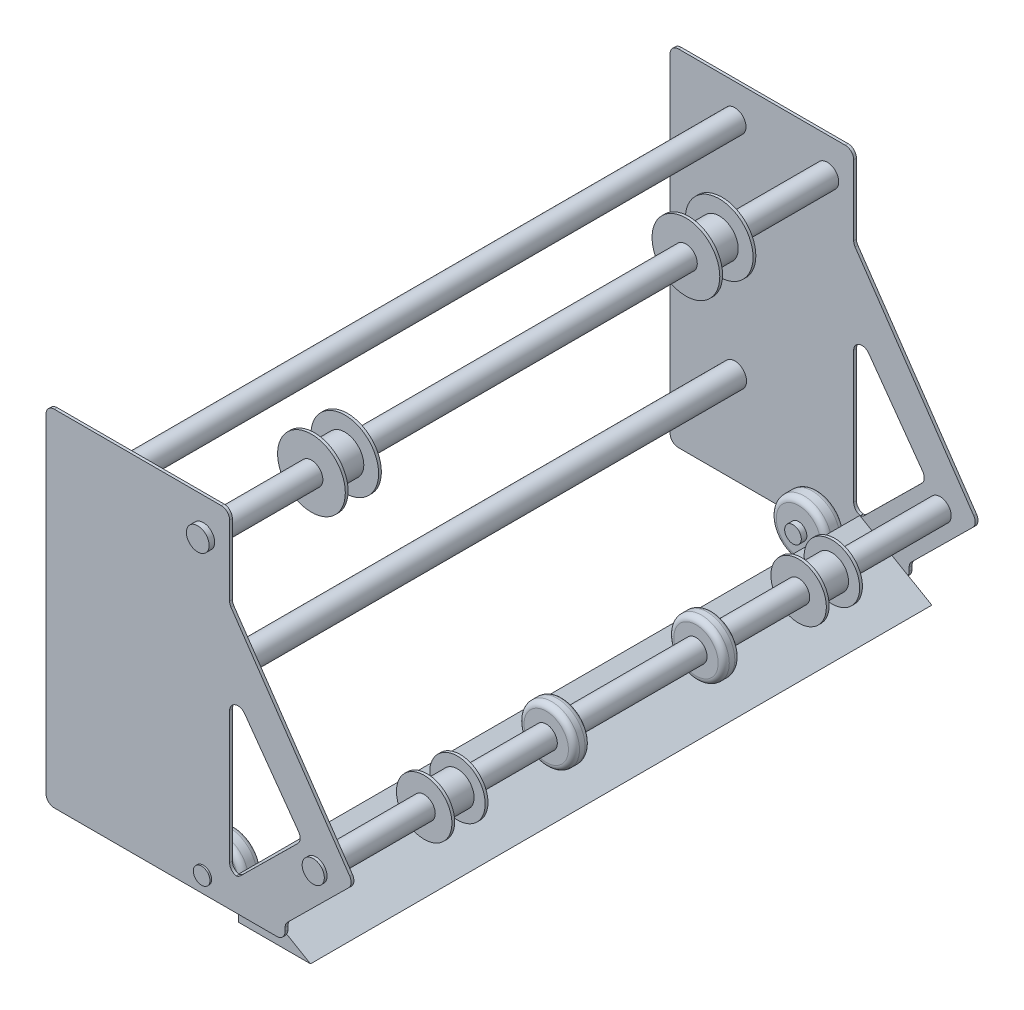
SolidWorks part; units mm, degrees
note: The reader was unsure of these and kept them because the rebuilt part matched: shared geometry of "Sketch10<2>", "Sketch10<3>", "Sketch14<2>".
ref_plane "Front Plane" through (0, 0, 0) normal (0, 0, 1) x (1, 0, 0)
ref_plane "Top Plane" through (0, 0, 0) normal (0, 1, 0) x (1, 0, 0)
ref_plane "Right Plane" through (0, 0, 0) normal (1, 0, 0) x (0, 0, -1)
sketch "Sketch1" plane through (0, 0, 0) normal (0, 0, 1) x (1, 0, 0)
  circle A0 centre (0, 0) radius 12.7
extrude "Boss-Extrude1" add sketch "Sketch1" along normal blind 8.89
fillet "Fillet1" radius 2.54 2 edges at (12.7, 0, 0) (12.7, 0, 8.89)
sketch "Sketch2" plane through (0, 0, 8.89) normal (0, 0, 1) x (1, 0, 0)
  circle A0 centre (0, 0) radius 3.81
extrude "Boss-Extrude2" add sketch "Sketch2" along normal blind 6.35 and the other way blind 11.43
sketch "Sketch3" plane through (0, 0, 15.24) normal (0, 0, 1) x (1, 0, 0)
  line L1 (-13.3576, -7.6281) -> (37.4424, -7.6281)
  line L2 (-13.3576, -7.6281) -> (-13.3576, 7.0012)
  line L3 (-13.3576, 7.0012) -> (37.4424, 7.0012)
  line L4 (37.4424, -7.6281) -> (37.4424, 7.0012)
  dimension "D1" = 50.8
extrude "Boss-Extrude3" add sketch "Sketch3" against normal blind 1.27 from offset 0.762 offset against normal yes
sketch "Sketch4" plane through (0, 0, 13.208) normal (0, 0, -1) x (-1, 0, 0)
  line L0 (-14.8354, 7.0012) -> (-14.8354, -12.0488)
  line L1 (-37.4424, 7.0012) -> (13.3576, 7.0012) construction
  line L2 (-14.8354, -12.0488) -> (-47.8309, -12.0488)
  line L3 (-47.8309, -12.0488) -> (-14.8354, 7.0012)
  dimension "D1" = 30
  dimension "D2" = 19.05
extrude "Boss-Extrude4" add sketch "Sketch4" along normal blind 142.24
sketch "Sketch8" plane through (0, 0, 14.478) normal (0, 0, 1) x (1, 0, 0)
  line L0 (15.9211, 7.0012) -> (30.3722, -7.6281)
  line L1 (15.9211, 7.0012) -> (54.3749, 44.9867)
  line L2 (30.3722, -7.6281) -> (68.826, 30.3574)
  line L3 (54.3749, 44.9867) -> (68.826, 30.3574)
  line L4 (37.4424, 7.0012) -> (-13.3576, 7.0012) construction
  line L5 (-13.3576, -7.6281) -> (37.4424, -7.6281) construction
extrude "Boss-Extrude7" add sketch "Sketch8" against normal blind 1.27
sketch "Sketch9" plane through (0, 0, 14.478) normal (0, 0, 1) x (1, 0, 0)
  line L3 (54.3749, 44.9867) -> (15.9211, 7.0012) construction
  line L4 (37.4424, -0.644) -> (68.826, 30.3574) construction
  circle A0 centre (51.6038, 27.7896) radius 5.08
  dimension "D1" = 0
  dimension "D2" = 10.287
other "AlignGroup2" parameters "D1"=6.2469, "D2"=16.5377, "D3"=20.5633, "D4"=20.574
extrude "Boss-Extrude8" add sketch "Sketch9" along normal blind 1.27 and the other way blind 143.51
sketch "Sketch10" plane through (0, 0, 15.748) normal (0, 0, 1) x (1, 0, 0)
  circle A0 centre (51.6038, 27.7896) radius 12.7
  dimension "D1" = 25.4
extrude "Boss-Extrude9" add sketch "Sketch10" against normal blind 1.27 from offset 50.8 offset against normal yes
sketch "Sketch11" plane through (0, 0, -35.052) normal (0, 0, 1) x (1, 0, 0)
  circle A0 centre (51.6038, 27.7896) radius 7.62
  dimension "D1" = 15.24
extrude "Boss-Extrude10" add sketch "Sketch11" against normal blind 15.24
extrude "Boss-Extrude11" add sketch "Sketch10<2>" against normal blind 1.27 from offset 66.04 offset against normal yes
sketch "Sketch10<2>" plane through (0, 0, 15.748) normal (0, 0, 1) x (1, 0, 0) same geometry as "Sketch10"
extrude "Boss-Extrude12" add sketch "Sketch10<3>" along normal blind 7.62 from offset 114.3 offset against normal yes
sketch "Sketch10<3>" plane through (0, 0, 15.748) normal (0, 0, 1) x (1, 0, 0) same geometry as "Sketch10"
fillet "Fillet2" radius 2.54 2 edges at (64.3038, 27.7896, -90.932) (64.3038, 27.7896, -98.552)
sketch "Sketch12" plane through (0, 0, 14.478) normal (0, 0, 1) x (1, 0, 0)
  line L0 (68.826, 30.3574) -> (-13.3576, 150.4993)
  line L1 (-13.3576, -7.6281) -> (12.0424, -7.6281)
  line L2 (-13.3576, -7.6281) -> (-13.3576, 150.4993)
  line L3 (-13.3576, 150.4993) -> (12.0424, 150.4993)
  line L4 (12.0424, -7.6281) -> (12.0424, 150.4993)
  line L5 (-13.3576, 118.3928) -> (57.6665, 19.3338)
  line L6 (37.4424, -0.644) -> (68.826, 30.3574) construction
  line M2 (54.3749, 44.9867) -> (15.9211, 7.0012)
  line M3 (15.9211, 7.0012) -> (-13.3576, 7.0012)
  line M8 (68.826, 30.3574) -> (54.3749, 44.9867)
extrude "Boss-Extrude13" add sketch "Sketch12" against normal blind 1.27 contours L2 L5 L4 L0 | L0 L4 L3 | L4 L5 L0 M2 M8 | L5 L2 L4 M3
sketch "Sketch13" plane through (0, 0, 15.748) normal (0, 0, 1) x (1, 0, 0)
  circle A0 centre (0, 134.4502) radius 5.207
  dimension "D1" = 10.414
extrude "Boss-Extrude14" add sketch "Sketch13" along normal blind 1.27 and the other way blind 146.05
sketch "Sketch14" plane through (0, 0, 14.478) normal (0, 0, 1) x (1, 0, 0)
  circle A0 centre (0, 134.4502) radius 15.5004
extrude "Boss-Extrude15" add sketch "Sketch14" against normal blind 1.27 from offset 49.53 offset against normal yes
extrude "Boss-Extrude16" add sketch "Sketch14<2>" against normal blind 1.27 from offset 64.77 offset against normal yes
sketch "Sketch14<2>" plane through (0, 0, 14.478) normal (0, 0, 1) x (1, 0, 0) same geometry as "Sketch14"
sketch "Sketch15" plane through (0, 0, 14.478) normal (0, 0, 1) x (1, 0, 0)
  circle A0 centre (0, 134.4502) radius 8.7177
extrude "Boss-Extrude17" add sketch "Sketch15" against normal blind 13.97 from offset 50.8 offset against normal yes
sketch "Sketch16" plane through (0, 0, 14.478) normal (0, 0, 1) x (1, 0, 0)
  line L1 (-13.3576, 150.4993) -> (-72.0219, 150.4993)
  line L2 (-13.3576, 150.4993) -> (-13.3576, -7.6281)
  line L3 (-13.3576, -7.6281) -> (-72.0219, -7.6281)
  line L4 (-72.0219, 150.4993) -> (-72.0219, -7.6281)
extrude "Boss-Extrude18" add sketch "Sketch16" against normal blind 1.27
sketch "Sketch17" plane through (0, 0, 14.478) normal (0, 0, 1) x (1, 0, 0)
  circle A0 centre (-42.371, 134.997) radius 5.1149
  circle A1 centre (-42.371, 34.3035) radius 5.3745
extrude "Boss-Extrude19" add sketch "Sketch17" against normal blind 144.78
mirror "Mirror1" about plane through (51.6038, 27.7896, -129.032) normal (0, 0, 1) of bodies 125
fillet "Fillet3" radius 3.81 28 edges at (12.0424, 150.4993, 13.843) (12.0424, 113.3677, 13.843) (45.5347, 36.2542, 13.843) (12.0424, 82.9668, 13.843) (12.0424, 7.0012, 13.843) (-72.0219, -7.6281, 13.843) (-72.0219, 150.4993, 13.843) (37.4424, -7.6281, 13.843) (13.4389, 7.0012, -271.272) (15.3782, 7.0012, -271.272) (15.9211, 7.0012, -271.907) (13.9817, 7.0012, -272.542) (37.4424, -0.644, -271.907) (37.4424, -7.6281, -271.907) (-72.0219, -7.6281, -271.907) (45.5347, 36.2542, -271.907) (12.0424, 150.4993, -271.907) (12.0424, 113.3677, -271.907) (68.826, 30.3574, -271.907) (12.0424, 82.9668, -271.907) (12.0424, 7.0012, -271.907) (-72.0219, 150.4993, -271.907) (13.4389, 7.0012, 13.208) (13.9817, 7.0012, 14.478) (15.3782, 7.0012, 13.208) (15.9211, 7.0012, 13.843) (37.4424, -0.644, 13.843) (68.826, 30.3574, 13.843)
